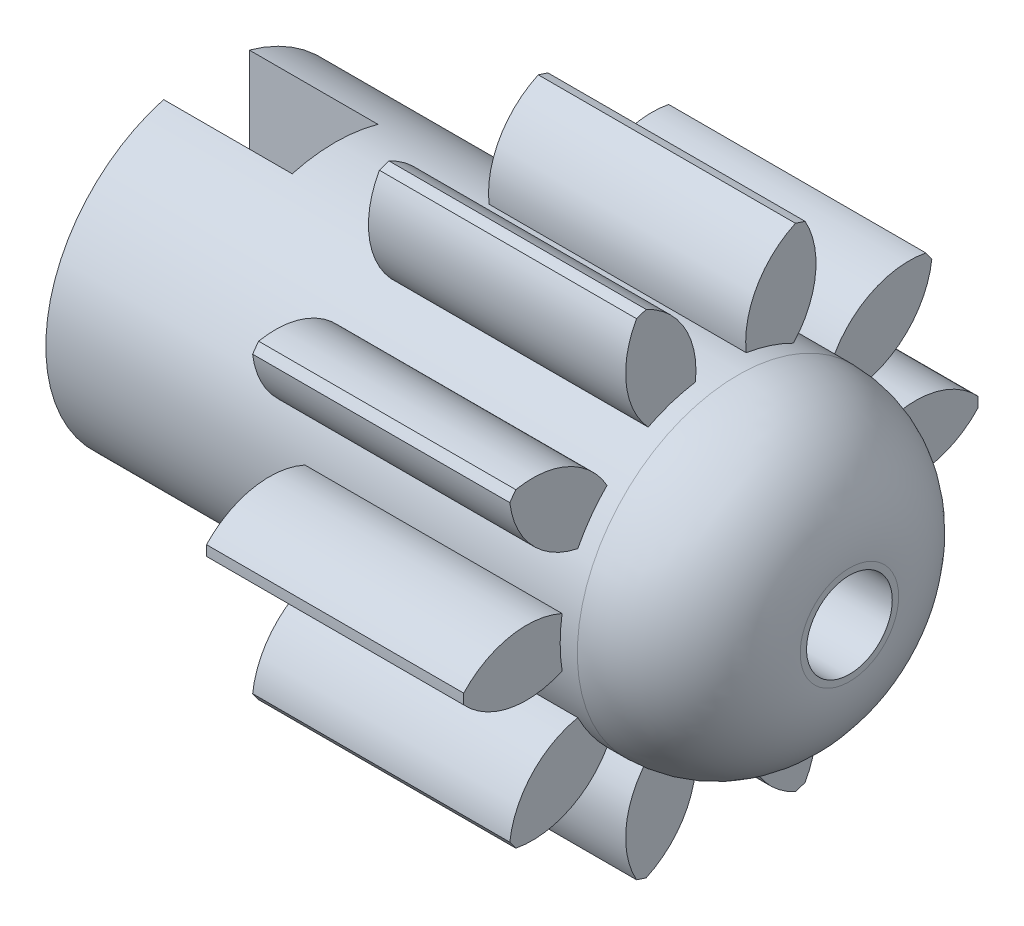
SolidWorks part; units mm, degrees
ref_plane "Plane1" through (0, 0, 0) normal (0, 0, 1) x (1, 0, 0)
ref_plane "Plane2" through (0, 0, 0) normal (0, 1, 0) x (1, 0, 0)
ref_plane "Plane3" through (0, 0, 0) normal (1, 0, 0) x (0, 0, -1)
other "Configuration Table"
sketch "HoldingSke" plane through (0, 0, 0) normal (0, 1, 0) x (1, 0, 0)
  line L0 (0, 0) -> (1.9696, -0.3473)
  line L1 (-15, 0) -> (100, 0) construction
  line L2 (0, 0) -> (-2.1039, 2.3779)
  line L3 (0, 0) -> (-11.863, 4.5341)
  line L4 (0, 0) -> (8.5048, 1.4996)
  line L5 (0, 0) -> (-46.8476, -17.4728)
  line L6 (0, 0) -> (-2.4869, -1.6779)
  line L7 (-2.1039, 2.3779) -> (8.6586, 51.2059)
  line L8 (-76.2, 54.61) -> (-76.1, 54.61)
  line L9 (-71.009, 38.7566) -> (-53.1078, 45.2721)
  line L10 (-76.2, 71.12) -> (104.1128, 71.12)
  line L11 (0, 0) -> (-3, 0)
  line L12 (-76.2, 101.6) -> (-76.181, 101.6)
  line L13 (24.9733, 27.94) -> (52.9518, 28.4284)
  line L14 (24.9733, 27.94) -> (24.9743, 27.94)
  line L15 (24.9733, 27.94) -> (100.4006, 29.5858)
  line L16 (-63.627, -0.5) -> (-12.827, -0.5)
  circle A0 centre (0, 0) radius 0.5
  circle A1 centre (0, 0) radius 1.874
  circle A2 centre (0, 0) radius 37.5
  circle A3 centre (0, 0) radius 0.5
  dimension "Num_teeth" = 10
  dimension "Pitch_radius" = 180.3128
  dimension "Width" = 3
  dimension "Thickness" = 3
sketch "BasProSke" plane through (0, 0, 0) normal (0, 1, 0) x (1, 0, 0)
  line L0 (-10, 0) -> (60, 0) construction
  line L1 (0, 0) -> (0, 3)
  line L2 (0, 0) -> (3, 0)
  line L3 (3, 0) -> (3, 3)
  line L4 (3, 3) -> (0, 3)
  dimension "Thickness" = 3
  dimension "Diameter" = 6
revolve "Base-Revolve" add sketch "BasProSke" angle 360 about L0
sketch "TooCutSke" plane through (0, 0, 0) normal (1, 0, 0) x (0, 0, -1)
  line L1 (0, 0) -> (0, 107) construction
  line L2 (0, 0) -> (-0.4243, 2.4637) construction
  line L3 (0, 0) -> (-1.5292, 4.7063) construction
  line L4 (-0.4243, 2.4637) -> (-0.7646, 2.3532) construction
  arc A0 (0.2964, 1.8504) -> (-0.2964, 1.8504) centre (0, 0) ccw
  arc A1 (0.9059, 2.8866) -> (-0.9059, 2.8866) centre (0, 0) ccw
  circle A2 centre (0, 0) radius 2.5 construction
  circle A3 centre (0, 0) radius 2.3492 construction
  arc A4 (-0.2964, 1.8504) -> (-0.9059, 2.8866) centre (-1.2901, 1.9633) ccw
  arc A5 (0.9059, 2.8866) -> (0.2964, 1.8504) centre (1.2901, 1.9633) ccw
extrude "ToothCut" cut sketch "TooCutSke" along normal through all
fillet "Breaks" [suppressed] radius 0.01 tangent propagation no
fillet "RootFillets" [suppressed] radius 0.126
pattern_circular "TeethCuts" count 10 every 36 about axis through (-10, 0, 0) along (1, 0, 0) of "ToothCut", "RootFillets", "Breaks"
sketch "HubNeaOneSke" plane through (0, 0, 0) normal (-1, 0, 0) x (0, 0, 1)
  circle A0 centre (0, 0) radius 1.874
  dimension "Diameter" = 3.748
extrude "HubNearOne" [suppressed] add sketch "HubNeaOneSke" along normal blind 47.0001
sketch "HubNeaBotSke" plane through (0, 0, 0) normal (-1, 0, 0) x (0, 0, 1)
  circle A0 centre (0, 0) radius 1.874
  dimension "Diameter" = 3.748
extrude "HubNearBoth" [suppressed] add sketch "HubNeaBotSke" along normal blind 23.5
ref_plane "FarPln" through (3, 0, 0) normal (1, 0, 0) x (0, 0, -1)
sketch "HubFarSke" plane through (3, 0, 0) normal (1, 0, 0) x (0, 0, -1)
  circle A0 centre (0, 0) radius 1.874
  dimension "Diameter" = 3.748
extrude "HubFar" [suppressed] add sketch "HubFarSke" along normal blind 23.5
sketch "BorSke" plane through (0, 0, 0) normal (1, 0, 0) x (0, 0, -1)
  circle A0 centre (0, 0) radius 0.5
  dimension "Diameter" = 1
extrude "Bore" cut sketch "BorSke" along normal mid plane 100.0001
sketch "KeySke" plane through (0, 0, 0) normal (1, 0, 0) x (0, 0, -1)
  line L0 (-0.05, 0) -> (-0.05, 0.6)
  line L1 (-0.05, 0.6) -> (0.05, 0.6)
  line L2 (0.05, 0.6) -> (0.05, 0)
  line L3 (0, 0) -> (0, 34) construction
  line L4 (-0.05, 0) -> (0.05, 0)
extrude "Keyway" [suppressed] cut sketch "KeySke" along normal mid plane 100.0001
pattern_circular "Keyway2" [suppressed] count 2 every 90 about axis through (-10, 0, 0) along (1, 0, 0)
sketch "草图1" plane through (3, 0, 0) normal (1, 0, 0) x (0, 0, -1)
  circle A0 centre (0, 0) radius 1.874
  circle A1 centre (0, 0) radius 0.5
extrude "凸台-拉伸1" add sketch "草图1" along normal blind 1.5
fillet "圆角2" radius 1.3 1 edges at (4.5, 0, -1.874)
sketch "草图2" plane through (0, 0, 0) normal (-1, 0, 0) x (0, 0, 1)
  circle A0 centre (0, 0) radius 0.5
  circle A1 centre (0, 0) radius 1.874
extrude "凸台-拉伸2" add sketch "草图2" along normal blind 3
sketch "草图3" plane through (-3, 0, 0) normal (-1, 0, 0) x (0, 0, 1)
  line L1 (-0.5, -1.8807) -> (0.5, -1.8807)
  line L2 (-0.5, -1.8807) -> (-0.5, 1.8807)
  line L3 (-0.5, 1.8807) -> (0.5, 1.8807)
  line L4 (0.5, -1.8807) -> (0.5, 1.8807)
  line L5 (-0.5, -1.8807) -> (0.5, 1.8807) construction
  line L6 (-0.5, 1.8807) -> (0.5, -1.8807) construction
  point P0 (0, 0)
extrude "切除-拉伸1" cut sketch "草图3" against normal blind 1.5
equation "' \"Module@HoldingSke\" = 6.35"
equation "' \"Num_teeth@HoldingSke\" = 12"
equation "' \"Ap@HoldingSke\" =  20"
equation "' \"Ap@HoldingSke\" = 20"
equation "' \"Width@HoldingSke\" = 0.5 * 25.4"
equation "' \"Hub_dia@HoldingSke\"= 1 * 25.4"
equation "' \"Hub_dia@HoldingSke\" = 1 * 25.4"
equation "' \"Overall_len@HoldingSke\" = 1.0 * 25.4"
equation "' \"Bore@HoldingSke\" = 0.75 * 25.4"
equation "' \"T_dim@HoldingSke\" = 0.1 * 25.4"
equation "' \"Width@KeySke\" = 0.25 * 25.4"
equation "' \"Show_teeth@HoldingSke\" = 13"
equation "' \"Backlash@HoldingSke\" = 0.009 * 25.4"
equation "' \"Addendum_fac@HoldingSke\" = 1.0"
equation "' \"Dedendum_fac@HoldingSke\" = 1.25"
equation "' \"Dedendum_add@HoldingSke\" = 0.00005 * 25.4"
equation "' \"Clearance_fac@HoldingSke\" = 0.25"
equation "\"Pitch@HoldingSke\" = 1 / \"Module@HoldingSke\""
equation "\"Overcut_dia@TooCutSke\" = (\"Num_teeth@HoldingSke\" + 2 * \"Addendum_fac@HoldingSke\") / \"Pitch@HoldingSke\" + 0.002 * 25.4"
equation "\"Pitch_dia@TooCutSke\" = \"Num_teeth@HoldingSke\" / \"Pitch@HoldingSke\""
equation "\"Base_dia@TooCutSke\" = \"Num_teeth@HoldingSke\" / \"Pitch@HoldingSke\" * cos((\"Ap@HoldingSke\"  * 3.14159265 / 180))"
equation "\"Root_dia@TooCutSke\" = (\"Num_teeth@HoldingSke\" + 2) / \"Pitch@HoldingSke\" - 2 * (\"Addendum_fac@HoldingSke\" + \"Dedendum_fac@HoldingSke\") / \"Pitch@HoldingSke\" - \"Dedendum_add@HoldingSke\" * 2"
equation "\"Half_ang@TooCutSke\" = 180 / \"Num_teeth@HoldingSke\""
equation "\"Half_CT@TooCutSke\" = \"Num_teeth@HoldingSke\" / \"Pitch@HoldingSke\" * sin((3.14159265 / 2 / \"Num_teeth@HoldingSke\")) / 2 - 7 * \"Backlash@HoldingSke\" / 4"
equation "\"Flank_rad@TooCutSke\" = \"Num_teeth@HoldingSke\" / \"Pitch@HoldingSke\" / 5"
equation "\"Radius@RootFillets\" = \"Clearance_fac@HoldingSke\" / \"Pitch@HoldingSke\" + \"Dedendum_add@HoldingSke\""
equation "\"Break_rad@Breaks\" = 0.02 / \"Pitch@HoldingSke\""
equation "\"Thickness@HoldingSke\" = \"Width@HoldingSke\""
equation "\"OAL@HoldingSke\" = \"Thickness@HoldingSke\""
equation "\"MHD@HoldingSke\" = (\"Num_teeth@HoldingSke\" + 2) / \"Pitch@HoldingSke\" - 2 * (\"Addendum_fac@HoldingSke\" + \"Dedendum_fac@HoldingSke\")  / \"Pitch@HoldingSke\" - \"Dedendum_add@HoldingSke\" * 2"
equation "\"MBD@HoldingSke\" = (\"Num_teeth@HoldingSke\" + 2) / \"Pitch@HoldingSke\" - 2 * (\"Addendum_fac@HoldingSke\" + \"Dedendum_fac@HoldingSke\")  / \"Pitch@HoldingSke\" - \"Dedendum_add@HoldingSke\" * 2 - 0.002 * 25.4"
equation "\"MHD@HoldingSke\" = ((sgn( \"MHD@HoldingSke\" - \"Hub_dia@HoldingSke\" )-1)*( \"MHD@HoldingSke\" - \"Hub_dia@HoldingSke\" ))/-2+ \"Hub_dia@HoldingSke\""
equation "\"MBD@HoldingSke\" = ((sgn( \"MBD@HoldingSke\" - \"Bore@HoldingSke\" )-1)*( \"MBD@HoldingSke\" - \"Bore@HoldingSke\" ))/-2+ \"Bore@HoldingSke\""
equation "\"OAL@HoldingSke\" = ((sgn( \"OAL@HoldingSke\" - \"Overall_len@HoldingSke\" )+1)*( \"OAL@HoldingSke\" - \"Overall_len@HoldingSke\" ))/2 + \"Overall_len@HoldingSke\" + 0.000002 * 25.4"
equation "\"Num_teeth@TeethCuts\" = int( \"Show_teeth@HoldingSke\" ) + 1"
equation "\"Num_teeth@TeethCuts\" = ((sgn( \"Num_teeth@TeethCuts\" - \"Num_teeth@HoldingSke\" )-1)*( \"Num_teeth@TeethCuts\" - \"Num_teeth@HoldingSke\" ))/-2+ \"Num_teeth@HoldingSke\""
equation "\"Num_teeth@TeethCuts\" = ((sgn( \"Num_teeth@TeethCuts\" - 2.0)+1)*( \"Num_teeth@TeethCuts\" - 2.0))/2 +2.0"
equation "\"Angle@TeethCuts\" = 360.0 / \"Num_teeth@HoldingSke\""
equation "\"Diameter@BasProSke\" = (\"Num_teeth@HoldingSke\" + 2 * \"Addendum_fac@HoldingSke\") / \"Pitch@HoldingSke\""
equation "\"Thickness@BasProSke\"  = \"Thickness@HoldingSke\""
equation "' \"Fillet_rad@BasProSke\" =  \"Thickness@HoldingSke\" * 0.05"
equation "' \"Fillet_rad@BasProSke\" = \"Thickness@HoldingSke\" * 0.05"
equation "\"MHD@HoldingSke\" = ((sgn( \"MHD@HoldingSke\" - \"Root_dia@TooCutSke\" )-1)*( \"MHD@HoldingSke\" - \"Root_dia@TooCutSke\" ))/-2+ \"Root_dia@TooCutSke\""
equation "\"Diameter@HubNeaOneSke\" = \"MHD@HoldingSke\""
equation "\"Length@HubNearOne\" = \"OAL@HoldingSke\" - \"Thickness@BasProSke\""
equation "\"Diameter@HubNeaBotSke\" = \"MHD@HoldingSke\""
equation "\"Length@HubNearBoth\" = ( \"OAL@HoldingSke\" - \"Thickness@BasProSke\" ) / 2.0"
equation "\"Thickness@FarPln\" = \"Thickness@BasProSke\""
equation "\"Diameter@HubFarSke\" = \"MHD@HoldingSke\""
equation "\"Length@HubFar\" = ( \"OAL@HoldingSke\" - \"Thickness@BasProSke\" ) / 2.0"
equation "\"Diameter@BorSke\" = \"MBD@HoldingSke\""
equation "\"D1@Bore\" = \"OAL@HoldingSke\" * 2.0"
equation "\"D1@Keyway\" = \"OAL@HoldingSke\" * 2.0"
equation "\"Offset@KeySke\" = \"T_dim@HoldingSke\" + \"MBD@HoldingSke\" / 2.0"
